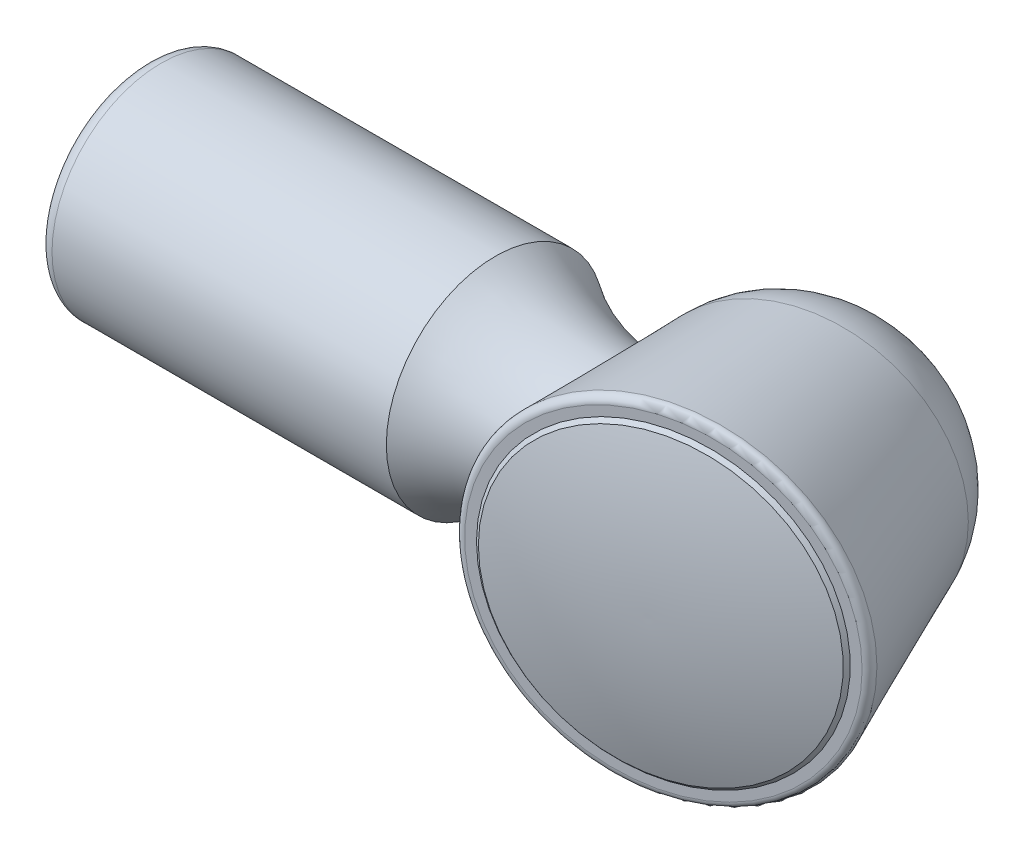
SolidWorks part; units mm, degrees
ref_plane "Front Plane" through (0, 0, 0) normal (0, 0, 1) x (1, 0, 0)
ref_plane "Top Plane" through (0, 0, 0) normal (0, 1, 0) x (1, 0, 0)
ref_plane "Right Plane" through (0, 0, 0) normal (1, 0, 0) x (0, 0, -1)
sketch "Sketch1" plane through (0, 0, 0) normal (1, 0, 0) x (0, 0, -1)
  circle A0 centre (0, 0) radius 19.05
  dimension "D1" = 38.1
extrude "Boss-Extrude1" add sketch "Sketch1" along normal mid plane 60.96
sketch "Sketch2" plane through (30.48, 0, 0) normal (1, 0, 0) x (0, 0, -1)
  circle A0 centre (0, 0) radius 12.7
  dimension "D1" = 25.4
extrude "Boss-Extrude2" add sketch "Sketch2" along normal blind 20.32
fillet "Fillet1" radius 35.56 1 edges at (30.48, 0, -12.7)
sketch "Sketch3" plane through (50.8, 0, 0) normal (1, 0, 0) x (0, 0, -1)
  line L0 (0, 12.7) -> (0, -12.7) construction
  circle A0 centre (0, 0) radius 12.7 construction
  circle A1 centre (0, 0) radius 12.7 construction
ref_plane "Plane1" through (3.403, 0, 12.7) normal (0.2588, 0, 0.9659) x (0, -1, 0)
sketch "Sketch4" plane through (3.403, 0, 12.7) normal (0.2588, 0, 0.9659) x (0, -1, 0)
  circle A0 centre (0, 71.12) radius 25.4
  dimension "D1" = 50.8
  dimension "D2" = 71.12
extrude "Boss-Extrude3" add sketch "Sketch4" along normal blind 25.4 draft 10 and the other way blind 25.4 draft 10 draft outward yes
fillet "Fillet2" radius 20.32 1 edges at (85.734, 0, -35.6566)
fillet "Fillet3" radius 1.27 1 edges at (107.5342, 0, 11.0941)
sketch "Sketch5" plane through (9.977, 0, 37.2345) normal (0.2588, 0, 0.9659) x (0.9659, 0, -0.2588)
  circle A0 centre (71.12, 0) radius 25.4
  dimension "D1" = 50.8
extrude "Cut-Extrude1" cut sketch "Sketch5" against normal blind 15.24 draft 10
fillet "Fillet4" radius 6.35 1 edges at (96.6681, 0, -1.7719)
sketch "Sketch6" plane through (9.977, 0, 37.2345) normal (0.2588, 0, 0.9659) x (0.9659, 0, -0.2588)
  line L0 (71.12, 25.4) -> (71.12, 0) construction
  circle A0 centre (71.12, 0) radius 25.4 construction
ref_plane "Plane2" through (68.6966, 0, -18.4072) normal (-0.9659, 0, 0.2588) x (0, -1, 0)
sketch "Sketch7" plane through (68.6966, 0, -18.4072) normal (-0.9659, 0, 0.2588) x (0, -1, 0)
  line L0 (0, 0) -> (0, 42.358) construction
  line L1 (-25.4, 38.548) -> (-26.67, 38.548)
  line L2 (-26.67, 38.548) -> (-26.035, 39.183)
  line L3 (-25.4, 38.548) -> (0, 38.548) construction
  line L4 (0, 42.358) -> (0, 41.088)
  line L5 (0, 41.088) -> (4.1324, 41.088) construction
  arc A0 (-26.035, 39.183) -> (0, 42.358) centre (-0.8213, -59.2387) cw
  arc A1 (0, 41.088) -> (-25.4, 38.548) centre (0, -87.182) ccw
  dimension "D5" = 101.6
  dimension "D1" = 3.81
  dimension "D2" = 0.635
  dimension "D3" = 0.635
  dimension "D4" = 1.27
  dimension "D6" = 1.27
revolve "Revolve1" add sketch "Sketch7" angle 360 about L0
fillet "Fillet5" radius 2.54 1 edges at (-30.48, 0, -19.05)
sketch "Sketch8" plane through (-30.48, 0, 0) normal (-1, 0, 0) x (0, 0, 1)
  circle A0 centre (0, 0) radius 12.7
  dimension "D1" = 25.4
extrude "Cut-Extrude2" cut sketch "Sketch8" against normal blind 25.4
